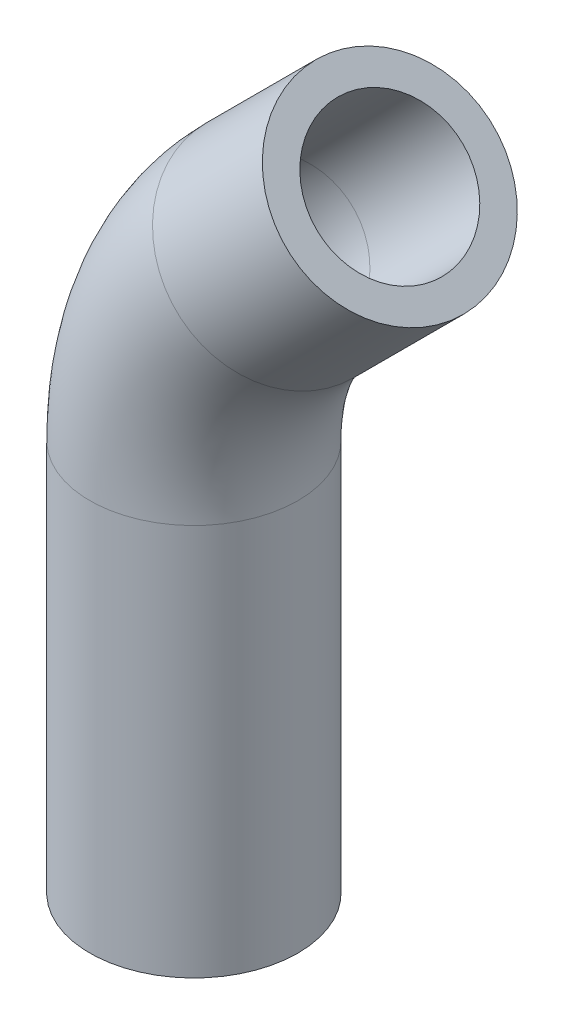
SolidWorks part; units mm, degrees
material "Silicon Rubber"
ref_plane "X-Y Datum" through (0, 0, 0) normal (0, 0, 1) x (1, 0, 0)
ref_plane "X-Z Datum" through (0, 0, 0) normal (0, 1, 0) x (1, 0, 0)
ref_plane "Y-Z Datum" through (0, 0, 0) normal (1, 0, 0) x (0, 0, -1)
sketch3d "3DSketch1"
  line L0 (0, 0, 0) -> (0, 50.8, 0)
  line L1 (11.1592, 77.7408, 0) -> (25.4, 91.9815, 0)
  arc A1 (0, 50.8, 0) -> (11.1592, 77.7408, 0) centre (38.1, 50.8, 0) cw
  point P4 (38.1, 50.8, -38.1)
  dimension "D2" = 45
  dimension "D1" = 38.1
  dimension "D3" = 25.4
  dimension "D4" = 50.8
sweep "Sweep1" add path "3DSketch1" circular profile diameter 26.9875 parameters "D3"=26.9875
sweep "Cut-Sweep1" cut path "3DSketch1<2>" circular profile diameter 19.05 parameters "D3"=19.05
sketch3d "3DSketch1<2>" same geometry as "3DSketch1"
